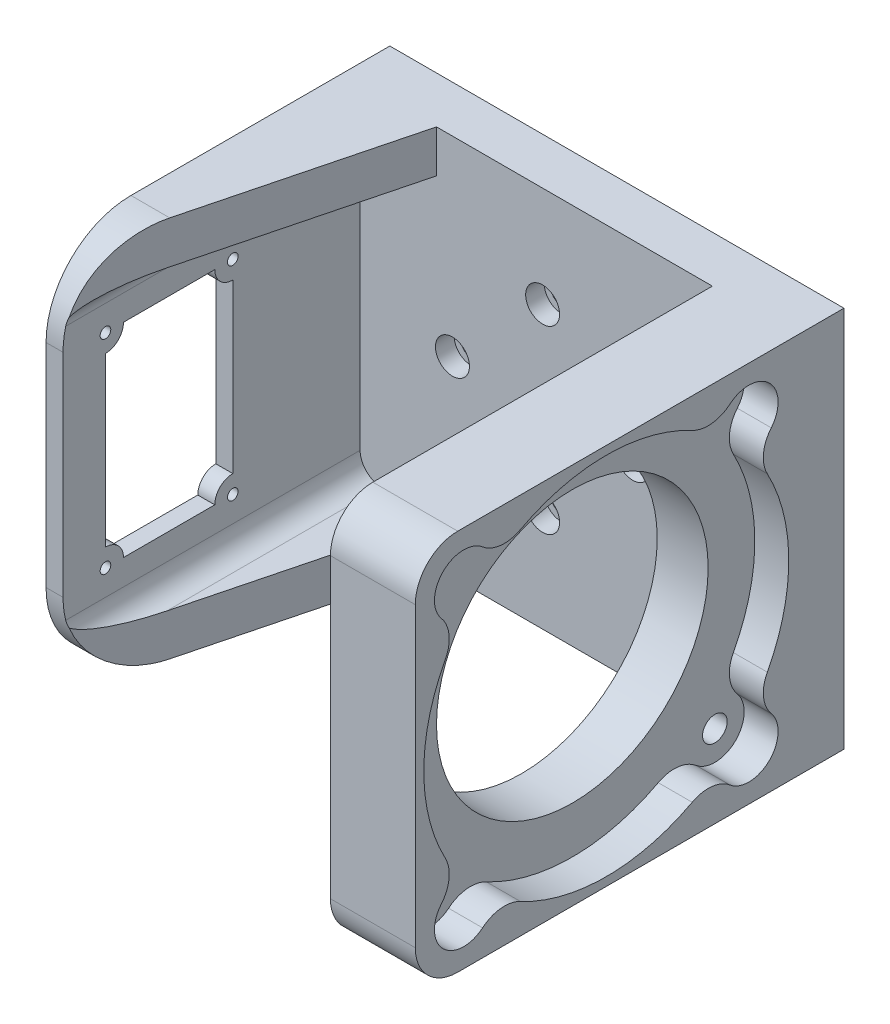
SolidWorks part; units mm, degrees
ref_plane "Front Plane" through (0, 0, 0) normal (0, 0, 1) x (1, 0, 0)
ref_plane "Top Plane" through (0, 0, 0) normal (0, 1, 0) x (1, 0, 0)
ref_plane "Right Plane" through (0, 0, 0) normal (1, 0, 0) x (0, 0, -1)
sketch "Sketch1" plane through (0, 0, 0) normal (0, 0, 1) x (1, 0, 0)
  line L1 (-60, -45) -> (60, -45)
  line L2 (-60, -45) -> (-60, 45)
  line L3 (-60, 45) -> (60, 45)
  line L4 (60, -45) -> (60, 45)
  line L5 (-60, -45) -> (60, 45) construction
  line L6 (-60, 45) -> (60, -45) construction
  circle A0 centre (0, 0) radius 41.25
  dimension "D1" = 82.5
  dimension "D2" = 90
  dimension "D3" = 120
extrude "Boss-Extrude1" add sketch "Sketch1" along normal blind 3
sketch "Sketch2" plane through (0, 0, 3) normal (0, 0, 1) x (1, 0, 0)
  line L4 (60, -45) -> (60, 45)
  line L5 (60, 45) -> (-60, 45)
  line L6 (-60, 45) -> (-60, -45)
  line L7 (-60, -45) -> (60, -45)
  line L8 (60, -45) -> (60, 45)
  line L9 (60, 45) -> (-60, 45)
  line L10 (-60, 45) -> (-60, -45)
  line L11 (-60, -45) -> (60, -45)
  dimension "D1" = 0
extrude "Boss-Extrude2" add sketch "Sketch2" along normal blind 8
hole_wizard "CBORE for M4 Hex Socket Head Cap Screw1" positions "Sketch3" profile "Sketch4" counterbore size "M4" standard "DIN" end condition through all
sketch "Sketch3" plane through (0, 0, 11) normal (0, 0, 1) x (1, 0, 0)
  circle A0 centre (0, 0) radius 21.25 construction
  point P5 (0, 21.25)
  point P11 (21.25, 0)
  point P12 (0, -21.25)
  point P13 (-21.25, 0)
  dimension "D1" = 42.5
  dimension "D2" = 4
sketch "Sketch4" plane through (-21.25, 0, 11) normal (1, 0, 0) x (0, -1, 0)
  line L0 (0, 0) -> (0, 11)
  line L1 (0, 11) -> (2.4, 11)
  line L3 (2.4, 11) -> (2.4, 4.4)
  line L4 (2.4, 4.4) -> (4, 4.4)
  line L5 (4, 4.4) -> (4, 0)
  line L7 (4, 0) -> (0, 0)
  line L11 (0, -6.35) -> (0, 107.95) construction
  dimension "Thru Hole Dia." = 4.8
  dimension "Thru Hole Depth" = 11
  dimension "C'Bore Dia." = 8
  dimension "C'Bore Depth" = 4.4
sketch "Sketch5" plane through (0, 0, 11) normal (0, 0, 1) x (1, 0, 0)
  line L0 (-60, -45) -> (60, -45) construction
  line L1 (60, 45) -> (40, 45)
  line L2 (60, 45) -> (60, -45)
  line L3 (60, -45) -> (40, -45)
  line L4 (40, 45) -> (40, -45)
  dimension "D1" = 20
extrude "Boss-Extrude3" add sketch "Sketch5" along normal blind 90
sketch "Sketch6" plane through (60, 0, 0) normal (1, 0, 0) x (0, 0, -1)
  line L0 (-101, 45) -> (-11, -45) construction
  line L1 (-11, 45) -> (-101, -45) construction
  line L4 (-11, -45) -> (-11, 45)
  line L5 (-101, -45) -> (-11, -45)
  line L6 (-101, 45) -> (-101, -45)
  line L7 (-11, 45) -> (-101, 45)
  line L8 (-11, -45) -> (-11, 45) construction
  line L9 (-101, -45) -> (-11, -45) construction
  line L10 (-101, 45) -> (-101, -45) construction
  line L11 (-11, 45) -> (-101, 45) construction
  circle A0 centre (-56, 0) radius 13.5
  dimension "D2" = 27
  dimension "D1" = 0
extrude "Cut-Extrude1" [suppressed] cut sketch "Sketch6" against normal blind 10
sketch "Sketch7" [suppressed] plane through (50, 0, 0) normal (1, 0, 0) x (0, 0, -1)
  circle A0 centre (-56, 0) radius 12.5
  circle A1 centre (-56, 0) radius 13.5 construction
  dimension "D1" = 25
extrude "Cut-Extrude2" [suppressed] cut sketch "Sketch7" against normal through all
sketch "Sketch8" plane through (40, 0, 0) normal (-1, 0, 0) x (0, 0, 1)
  line L0 (11, 45) -> (101, -45) construction
  line L1 (101, 45) -> (11, -45) construction
  line L4 (11, 45) -> (11, -45)
  line L5 (11, -45) -> (101, -45)
  line L6 (101, -45) -> (101, 45)
  line L7 (101, 45) -> (11, 45)
  line L8 (11, 45) -> (11, -45) construction
  line L9 (11, -45) -> (101, -45) construction
  line L10 (101, -45) -> (101, 45) construction
  line L11 (101, 45) -> (11, 45) construction
  circle A0 centre (56, 0) radius 32
  dimension "D2" = 64
  dimension "D1" = 0
extrude "Cut-Extrude3" cut sketch "Sketch8" against normal through all
hole_wizard "M5 Clearance Hole1" positions "Sketch10" profile "Sketch12" hole size "M5" standard "DIN" end condition through all
sketch "Sketch10" plane through (60, 0, 0) normal (1, 0, 0) x (0, 0, -1)
  line L0 (-56, 0) -> (-89.5876, -33.5876) construction
  circle A0 centre (-56, 0) radius 47.5 construction
  point P7 (-89.5876, -33.5876)
  point P17 (-89.5876, 33.5876)
  point P18 (-22.4124, 33.5876)
  point P19 (-22.4124, -33.5876)
  dimension "D1" = 95
  dimension "D2" = 4
sketch "Sketch12" plane through (60, -33.5876, 22.4124) normal (0, 1, 0) x (0, 0, -1)
  line L0 (0, 0) -> (0, 120)
  line L1 (0, 120) -> (2.9, 120)
  line L2 (2.9, 120) -> (2.9, 0)
  line L5 (2.9, 0) -> (0, 0)
  line L11 (0, -6.35) -> (0, 107.95) construction
  dimension "Thru Hole Dia." = 5.8
  dimension "Thru Hole Depth" = 120
sketch "Sketch13" plane through (60, 0, 0) normal (1, 0, 0) x (0, 0, -1)
  circle A0 centre (-56, 0) radius 32 construction
  circle A1 centre (-56, 0) radius 32
  circle A2 centre (-56, 0) radius 43
  circle A3 centre (-22.4124, -33.5876) radius 2.9 construction
  circle A4 centre (-22.4124, 33.5876) radius 2.9 construction
  circle A6 centre (-89.5876, -33.5876) radius 2.9 construction
  circle A7 centre (-22.4124, -33.5876) radius 2.9
  circle A8 centre (-22.4124, 33.5876) radius 2.9 construction
  circle A9 centre (-89.5876, 33.5876) radius 2.9 construction
  circle A10 centre (-89.5876, -33.5876) radius 2.9 construction
  circle A11 centre (-89.5876, 33.5876) radius 6.9
  circle A12 centre (-89.5876, -33.5876) radius 6.9
  circle A13 centre (-22.4124, -33.5876) radius 6.9
  circle A14 centre (-22.4124, 33.5876) radius 6.9
  circle A15 centre (-89.5876, 33.5876) radius 2.9 construction
  circle M3 centre (-89.5876, -33.5876) radius 2.9
  circle M4 centre (-89.5876, 33.5876) radius 2.9
  circle M5 centre (-22.4124, 33.5876) radius 2.9
  circle M6 centre (-22.4124, -33.5876) radius 2.9
  circle M7 centre (-56, 0) radius 32
  dimension "D1" = 11
  dimension "D2" = 4
extrude "Cut-Extrude4" cut sketch "Sketch13" against normal blind 8 contours A2 A11 M4 | A2 A11 | A14 A2 A11 A12 A13 M7 | A2 A14 | A2 A14 M5 | A2 A13 | A2 A13 M6 | A2 A12 | A2 A12 M3 region at (60, -13.7292, 16.5362) region at (60, 29.676, 26.324) region at (60, 30.5436, 25.4564) region at (60, -28.8906, 17.6278) region at (60, -29.676, 26.324) region at (60, 29.676, 85.676) region at (60, 30.5436, 86.5436) region at (60, -38.3286, 94.3286) region at (60, -29.676, 85.676)
fillet "Fillet1" radius 8 8 edges at (56, -33.7151, 29.3112) (56, -26.6888, 22.2849) (56, -33.7151, 82.6888) (56, 26.6888, 89.7151) (56, -26.6888, 89.7151) (56, 26.6888, 22.2849) (56, 33.7151, 29.3112) (56, 33.7151, 82.6888)
sketch "Sketch14" plane through (0, 0, 11) normal (0, 0, 1) x (1, 0, 0)
  line L0 (-60, -45) -> (40, -45) construction
  line L1 (-60, 45) -> (-43, 45)
  line L2 (-60, 45) -> (-60, -45)
  line L3 (-60, -45) -> (-43, -45)
  line L4 (-43, 45) -> (-43, -45)
  dimension "D1" = 17
extrude "Boss-Extrude4" add sketch "Sketch14" along normal blind 70
hole_wizard "Tap Drill for M3 Tap2" positions "Sketch18" profile "Sketch19" hole size "M3" standard "DIN" end condition through all
sketch "Sketch18" plane through (-43, 0, 0) normal (1, 0, 0) x (0, 0, -1)
  line L1 (-41, -24) -> (-71, -24)
  line L2 (-41, -24) -> (-41, 24)
  line L3 (-41, 24) -> (-71, 24)
  line L4 (-71, -24) -> (-71, 24)
  line L5 (-41, -24) -> (-71, 24) construction
  line L6 (-41, 24) -> (-71, -24) construction
  circle A0 centre (-56, 0) radius 32 construction
  circle A1 centre (-56, 0) radius 32
  point P5 (-71, 24)
  point P8 (-41, -24)
  point P9 (-41, 24)
  point P10 (-71, -24)
  dimension "D1" = 48
  dimension "D2" = 30
sketch "Sketch19" plane through (-43, -24, 71) normal (0, 1, 0) x (0, 0, -1)
  line L0 (0, 0) -> (0, 17)
  line L1 (0, 17) -> (1.25, 17)
  line L2 (1.25, 17) -> (1.25, 0)
  line L5 (1.25, 0) -> (0, 0)
  line L11 (0, -6.35) -> (0, 107.95) construction
  dimension "Thru Hole Dia." = 2.5
  dimension "Thru Hole Depth" = 17
sketch "Sketch20" plane through (-43, 0, 0) normal (1, 0, 0) x (0, 0, -1)
  line L0 (-71, 19.75) -> (-71, -19.75)
  line L1 (-66.75, -24) -> (-45.25, -24)
  line L2 (-41, -19.75) -> (-41, 19.75)
  line L3 (-45.25, 24) -> (-66.75, 24)
  circle A0 centre (-71, -24) radius 1.25 construction
  circle A1 centre (-41, -24) radius 1.25 construction
  circle A2 centre (-41, 24) radius 1.25 construction
  circle A3 centre (-71, 24) radius 1.25 construction
  circle A12 centre (-71, -24) radius 1.25
  circle A13 centre (-41, -24) radius 1.25
  circle A14 centre (-41, 24) radius 1.25
  circle A15 centre (-71, 24) radius 1.25
  circle A16 centre (-71, -24) radius 4.25
  circle A17 centre (-41, -24) radius 4.25
  circle A18 centre (-41, 24) radius 4.25
  circle A19 centre (-71, 24) radius 4.25
  dimension "D1" = 3
extrude "Cut-Extrude5" cut sketch "Sketch20" against normal through all contours A19 L0 A16 L1 A17 L2 A18 L3 region at (-43, 0, 56)
sketch "Sketch21" plane through (-60, 0, 0) normal (-1, 0, 0) x (0, 0, 1)
  line L4 (0, 45) -> (0, -45)
  line L5 (0, -45) -> (81, -45)
  line L6 (81, -45) -> (81, 45)
  line L7 (81, 45) -> (0, 45)
  line L8 (0, 45) -> (0, -45)
  line L9 (0, -45) -> (81, -45)
  line L10 (81, -45) -> (81, 45)
  line L11 (81, 45) -> (0, 45)
  dimension "D1" = 0
extrude "Cut-Extrude6" cut sketch "Sketch21" against normal blind 13
sketch "Sketch22" plane through (0, -45, 0) normal (0, -1, 0) x (1, 0, 0)
  line L0 (-43, 81) -> (-25, 11)
  line L1 (-43, 11) -> (40, 11) construction
  line L2 (-25, 11) -> (-43, 11)
  line L3 (-43, 11) -> (-43, 81)
  dimension "D1" = 18
extrude "Boss-Extrude5" add sketch "Sketch22" against normal blind 10
extrude "Boss-Extrude6" add sketch "Sketch22<2>" along normal blind 10 from surface starting at face at (2.5, 45, 48.25)
sketch "Sketch22<2>" plane through (0, -45, 0) normal (0, -1, 0) x (1, 0, 0) same geometry as "Sketch22"
fillet "Fillet3" radius 5 2 edges at (-43, -35, 46) (-43, 35, 46)
fillet "Fillet2" radius 20 2 edges at (-45, 45, 81) (-45, -45, 81)
fillet "Fillet4" radius 10 2 edges at (50, 45, 101) (50, -45, 101)
